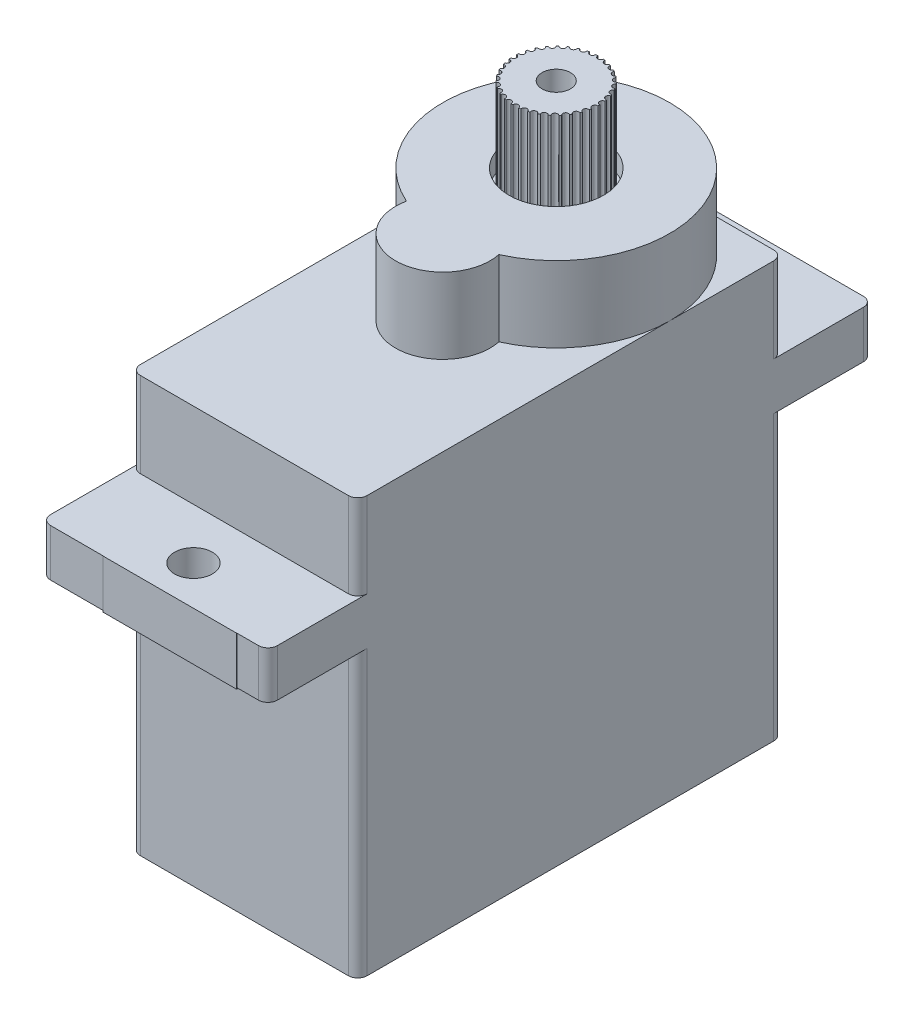
SolidWorks part; units mm, degrees
material "ABS PC"
ref_plane "Ön Düzlem" through (0, 0, 0) normal (0, 0, 1) x (1, 0, 0)
ref_plane "Üst Düzlem" through (0, 0, 0) normal (0, 1, 0) x (1, 0, 0)
ref_plane "Sağ Düzlem" through (0, 0, 0) normal (1, 0, 0) x (0, 0, -1)
sketch "Çizim1" plane through (0, 0, 0) normal (0, 1, 0) x (1, 0, 0)
  line L1 (-5.5, 11.25) -> (5.5, 11.25)
  line L2 (-6, 10.75) -> (-6, -10.75)
  line L3 (-5.5, -11.25) -> (5.5, -11.25)
  line L4 (6, 10.75) -> (6, -10.75)
  line L5 (-6, 11.25) -> (6, -11.25) construction
  line L6 (-6, -11.25) -> (6, 11.25) construction
  arc A0 (5.5, -11.25) -> (6, -10.75) centre (5.5, -10.75) ccw
  arc A1 (-6, -10.75) -> (-5.5, -11.25) centre (-5.5, -10.75) ccw
  arc A2 (5.5, 11.25) -> (6, 10.75) centre (5.5, 10.75) cw
  arc A3 (-5.5, 11.25) -> (-6, 10.75) centre (-5.5, 10.75) ccw
  point P0 (0, 0)
  dimension "D3" = 0.5
  dimension "D1" = 12
  dimension "D2" = 22.5
extrude "Yükseklik-Ekstrüzyon1" add sketch "Çizim1" along normal blind 1
sketch "Çizim2" plane through (0, 1, 0) normal (0, 1, 0) x (1, 0, 0)
  line L0 (-5, 9.25) -> (-5, -9.25)
  line L1 (-5.5, 11.25) -> (5.5, 11.25)
  line L2 (-6, 10.75) -> (-6, -10.75)
  line L3 (-5.5, -11.25) -> (5.5, -11.25)
  line L4 (6, 10.75) -> (6, -10.75)
  line L5 (-6, 11.25) -> (-5.8961, 11.0552) construction
  line L6 (-6, -11.25) -> (-5.8961, -11.0552) construction
  line L7 (-4, -10.25) -> (4, -10.25)
  line L8 (5, 9.25) -> (5, -9.25)
  line L9 (-4, 10.25) -> (4, 10.25)
  line L10 (-6, -11.25) -> (6, -11.25) construction
  line L11 (6, 11.25) -> (6, -11.25) construction
  line L12 (-6, 11.25) -> (-6, -11.25) construction
  line L13 (-6, 11.25) -> (6, 11.25) construction
  line L14 (-5, 10.25) -> (5, 10.25) construction
  line L15 (-5, 10.25) -> (-5, -10.25) construction
  line L16 (-4.9345, 9.2521) -> (4.9345, -9.2521) construction
  line L17 (5, 10.25) -> (5, -10.25) construction
  line L18 (5.8961, 11.0552) -> (6, 11.25) construction
  line L19 (-5, -10.25) -> (5, -10.25) construction
  line L20 (5.8961, -11.0552) -> (6, -11.25) construction
  line L21 (-4.9345, -9.2521) -> (4.9345, 9.2521) construction
  arc A0 (5.5, -11.25) -> (6, -10.75) centre (5.5, -10.75) ccw
  arc A1 (-6, -10.75) -> (-5.5, -11.25) centre (-5.5, -10.75) ccw
  arc A2 (5.5, 11.25) -> (6, 10.75) centre (5.5, 10.75) cw
  arc A3 (-5.5, 11.25) -> (-6, 10.75) centre (-5.5, 10.75) ccw
  arc A5 (4, 10.25) -> (5, 9.25) centre (5, 10.25) ccw
  arc A7 (-4, -10.25) -> (-5, -9.25) centre (-5, -10.25) ccw
  arc A8 (-5, 9.25) -> (-4, 10.25) centre (-5, 10.25) ccw
  arc A9 (5, -9.25) -> (4, -10.25) centre (5, -10.25) ccw
  point P0 (0, 0)
  dimension "D2" = 0.5
  dimension "D1" = 1
extrude "Yükseklik-Ekstrüzyon2" add sketch "Çizim2" along normal blind 5
sketch "Çizim3" plane through (0, 6, 0) normal (0, 1, 0) x (1, 0, 0)
  line L0 (0, -10.25) -> (0, -11.25) construction
  line L1 (-4, -10.25) -> (4, -10.25) construction
  line L2 (-5.5, -11.25) -> (5.5, -11.25) construction
  line L3 (0, -11.25) -> (0, -10.75) construction
  line L4 (0, -10.75) -> (2.4368, -10.75) construction
  line L6 (-2, -10.25) -> (2, -10.25)
  line L7 (-2, -10.25) -> (-2, -11.25)
  line L8 (-2, -11.25) -> (2, -11.25)
  line L9 (2, -10.25) -> (2, -11.25)
  line L10 (-2, -10.25) -> (2, -11.25) construction
  line L11 (-2, -11.25) -> (2, -10.25) construction
  dimension "D1" = 4
extrude "Kes-Ekstrüzyon1" cut sketch "Çizim3" against normal blind 1
fillet "Radyus1" radius 0.1 2 edges at (2, 5, 10.75) (-2, 5, 10.75)
sketch "Çizim4" plane through (0, 6, 0) normal (0, 1, 0) x (1, 0, 0)
  line L0 (-4, 10.25) -> (4, 10.25)
  line L1 (-5.5, 11.25) -> (5.5, 11.25)
  line L2 (-6, 10.75) -> (-6, -10.75)
  line L3 (-5.5, -11.25) -> (5.5, -11.25)
  line L4 (6, 10.75) -> (6, -10.75)
  line L5 (-6, 11.25) -> (-5.8961, 11.0552) construction
  line L6 (-6, -11.25) -> (-5.8961, -11.0552) construction
  line L7 (-4, 10.25) -> (4, 10.25)
  line L8 (5, 9.25) -> (5, -9.25)
  line L9 (5, -9.25) -> (5, 9.25)
  line L10 (-4, 10.25) -> (4, 10.25)
  line L11 (5, 9.25) -> (5, -9.25)
  line L12 (-4, -10.25) -> (4, -10.25)
  line L13 (-5, 9.25) -> (-5, -9.25)
  line L14 (-4.9345, 9.2521) -> (4.9345, -9.2521) construction
  line L15 (-5, 10.25) -> (-5, -10.25) construction
  line L16 (-5, 10.25) -> (5, 10.25) construction
  line L17 (5, 10.25) -> (5, -10.25) construction
  line L18 (5.8961, 11.0552) -> (6, 11.25) construction
  line L19 (5.8961, -11.0552) -> (6, -11.25) construction
  line L20 (-5, -10.25) -> (5, -10.25) construction
  line L21 (-4.9345, -9.2521) -> (4.9345, 9.2521) construction
  arc A0 (5.5, -11.25) -> (6, -10.75) centre (5.5, -10.75) ccw
  arc A1 (-6, -10.75) -> (-5.5, -11.25) centre (-5.5, -10.75) ccw
  arc A2 (5.5, 11.25) -> (6, 10.75) centre (5.5, 10.75) cw
  arc A3 (-5.5, 11.25) -> (-6, 10.75) centre (-5.5, 10.75) ccw
  arc A4 (-5, 9.25) -> (-4, 10.25) centre (-5, 10.25) ccw
  arc A5 (4, 10.25) -> (5, 9.25) centre (5, 10.25) ccw
  arc A6 (-4, -10.25) -> (-5, -9.25) centre (-5, -10.25) ccw
  arc A7 (5, -9.25) -> (4, -10.25) centre (5, -10.25) ccw
  arc A8 (5, 10.25) -> (5, 10.25) centre (5, 10.25) cw
  arc A9 (5, -10.25) -> (5, -10.25) centre (5, -10.25) ccw
  arc A10 (-5, -10.25) -> (-5, -10.25) centre (-5, -10.25) ccw
  arc A11 (-5, 10.25) -> (-5, 10.25) centre (-5, 10.25) ccw
  point P0 (0, 0)
  line M12 (4, -10.25) -> (2, -10.25)
  line M14 (2, -11.25) -> (5.5, -11.25)
  arc M15 (5.5, -11.25) -> (6, -10.75) centre (5.5, -10.75) ccw
  line M16 (6, -10.75) -> (6, 10.75)
  arc M17 (6, 10.75) -> (5.5, 11.25) centre (5.5, 10.75) ccw
  line M18 (5.5, 11.25) -> (-5.5, 11.25)
  arc M19 (-5.5, 11.25) -> (-6, 10.75) centre (-5.5, 10.75) ccw
  line M20 (-6, 10.75) -> (-6, -10.75)
  arc M21 (-6, -10.75) -> (-5.5, -11.25) centre (-5.5, -10.75) ccw
  line M22 (-5.5, -11.25) -> (-2, -11.25)
  line M24 (-2, -10.25) -> (-4, -10.25)
  arc M25 (-4, -10.25) -> (-5, -9.25) centre (-5, -10.25) ccw
  line M26 (-5, -9.25) -> (-5, 9.25)
  arc M27 (-5, 9.25) -> (-4, 10.25) centre (-5, 10.25) ccw
  line M28 (-4, 10.25) -> (4, 10.25)
  arc M29 (4, 10.25) -> (5, 9.25) centre (5, 10.25) ccw
  line M30 (5, 9.25) -> (5, -9.25)
  arc M31 (5, -9.25) -> (4, -10.25) centre (5, -10.25) ccw
  dimension "D1" = 0.5
  dimension "D2" = 1
extrude "Yükseklik-Ekstrüzyon4" add sketch "Çizim4" along normal blind 9 contours M31 M12 M14 M15 M16 M17 M18 M19 M20 M21 M22 M24 M25 M26 M27 M28 M29 M30 | L12 L3 region at (0, 6, -10.995)
sketch "Çizim6" plane through (0, 15, 0) normal (0, 1, 0) x (1, 0, 0)
  line L0 (0, -10.25) -> (0, -12.25) construction
  line L1 (-5.5, 16) -> (-0.7, 16)
  line L2 (-6, 15.5) -> (-6, -15.5)
  line L3 (-5.5, -16) -> (-0.7, -16)
  line L4 (6, 15.5) -> (6, -15.5)
  line L5 (-6, 16) -> (6, -16) construction
  line L6 (-3.8437, -10.25) -> (6, 16) construction
  line L7 (-4, 10.25) -> (4, 10.25)
  line L8 (-5, 9.25) -> (-5, -9.25)
  line L9 (-4, -10.25) -> (4, -10.25)
  line L10 (5, 9.25) -> (5, -9.25)
  line L11 (-4.5616, 9.3512) -> (4.5616, -9.3512) construction
  line L12 (-4.5616, -9.3512) -> (4.5616, 9.3512) construction
  line L13 (0, -12.25) -> (0, -11.25) construction
  line L14 (-5.5, -11.25) -> (5.5, -11.25) construction
  line L15 (0, -11.25) -> (8.7476, -11.25) construction
  line L16 (0, -12.25) -> (8.7476, -12.25) construction
  line L17 (0.7, -16) -> (5.5, -16)
  line L18 (-0.5, -14.2247) -> (-0.5, -15.8)
  line L19 (0.5, -14.2247) -> (0.5, -15.8)
  line L20 (0, 0) -> (5, 0) construction
  line L21 (0.5, 14.2247) -> (0.5, 15.8)
  line L22 (-0.5, 14.2247) -> (-0.5, 15.8)
  line L23 (0.7, 16) -> (5.5, 16)
  arc A0 (-5, 9.25) -> (-4, 10.25) centre (-5, 10.25) ccw
  arc A1 (4, 10.25) -> (5, 9.25) centre (5, 10.25) ccw
  arc A2 (5, -9.25) -> (4, -10.25) centre (5, -10.25) ccw
  arc A3 (-4, -10.25) -> (-5, -9.25) centre (-5, -10.25) ccw
  arc A4 (5.5, -16) -> (6, -15.5) centre (5.5, -15.5) ccw
  arc A5 (-6, -15.5) -> (-5.5, -16) centre (-5.5, -15.5) ccw
  arc A6 (5.5, 16) -> (6, 15.5) centre (5.5, 15.5) cw
  arc A7 (-5.5, 16) -> (-6, 15.5) centre (-5.5, 15.5) ccw
  arc A9 (0.5833, -14.0622) -> (-0.5833, -14.0622) centre (0, -13.25) ccw
  arc A10 (0.5, -14.2247) -> (0.5833, -14.0622) centre (0.7, -14.2247) cw
  arc A11 (-0.5, -14.2247) -> (-0.5833, -14.0622) centre (-0.7, -14.2247) ccw
  arc A12 (0.5, -15.8) -> (0.7, -16) centre (0.7, -15.8) ccw
  arc A13 (-0.5, -15.8) -> (-0.7, -16) centre (-0.7, -15.8) cw
  arc A14 (0.5, 15.8) -> (0.7, 16) centre (0.7, 15.8) cw
  arc A15 (-0.5, 15.8) -> (-0.7, 16) centre (-0.7, 15.8) ccw
  arc A16 (0.5, 14.2247) -> (0.5833, 14.0622) centre (0.7, 14.2247) ccw
  arc A17 (-0.5, 14.2247) -> (-0.5833, 14.0622) centre (-0.7, 14.2247) cw
  arc A18 (0.5833, 14.0622) -> (-0.5833, 14.0622) centre (0, 13.25) cw
  point P0 (0, 0)
  point P6 (0, 0)
  point P54 (0.5, -16)
  dimension "D2" = 0.5
  dimension "D4" = 2
  dimension "D5" = 0.2
  dimension "D1" = 32
  dimension "D3" = 1
extrude "Yükseklik-Ekstrüzyon5" add sketch "Çizim6" along normal blind 2.5
sketch "Çizim7" plane through (0, 17.5, 0) normal (0, 1, 0) x (1, 0, 0)
  line L0 (6, -15.5) -> (6, 15.5) construction
  line L1 (-5.5, 11.25) -> (5.5, 11.25)
  line L2 (-6, 10.75) -> (-6, -10.75)
  line L3 (-5.5, -11.25) -> (5.5, -11.25)
  line L4 (6, 10.75) -> (6, -10.75)
  line L5 (-6, 11.25) -> (-5.8961, 11.0552) construction
  line L6 (-6, -11.25) -> (-5.8961, -11.0552) construction
  line L7 (-5, 9.25) -> (-5, -9.25)
  line L8 (-4, 10.25) -> (4, 10.25)
  line L9 (5, 9.25) -> (5, -9.25)
  line L10 (4, -10.25) -> (-4, -10.25)
  line L12 (-4.9345, 9.2521) -> (4.9345, -9.2521) construction
  line L13 (5.8961, 11.0552) -> (6, 11.25) construction
  line L14 (5.8961, -11.0552) -> (6, -11.25) construction
  line L15 (-5, -9.25) -> (-5, 9.25)
  line L16 (-4.9345, -9.2521) -> (4.9345, 9.2521) construction
  line L17 (-5, 9.25) -> (-5, -9.25)
  arc A0 (-6, -10.75) -> (-5.5, -11.25) centre (-5.5, -10.75) ccw
  arc A1 (5.5, -11.25) -> (6, -10.75) centre (5.5, -10.75) ccw
  arc A2 (5.5, 11.25) -> (6, 10.75) centre (5.5, 10.75) cw
  arc A3 (-5.5, 11.25) -> (-6, 10.75) centre (-5.5, 10.75) ccw
  arc A4 (-5, 9.25) -> (-4, 10.25) centre (-5, 10.25) ccw
  arc A5 (4, 10.25) -> (5, 9.25) centre (5, 10.25) ccw
  arc A6 (5, -9.25) -> (4, -10.25) centre (5, -10.25) ccw
  arc A8 (-4, -10.25) -> (-5, -9.25) centre (-5, -10.25) ccw
  point P0 (0, 0)
  line M16 (6, -15.5) -> (6, 15.5)
  line M28 (-6, 15.5) -> (-6, -15.5)
  line M39 (-5, -9.25) -> (-5, 9.25)
  arc M40 (-5, 9.25) -> (-4, 10.25) centre (-5, 10.25) ccw
  line M41 (-4, 10.25) -> (4, 10.25)
  arc M42 (4, 10.25) -> (5, 9.25) centre (5, 10.25) ccw
  line M43 (5, 9.25) -> (5, -9.25)
  arc M44 (5, -9.25) -> (4, -10.25) centre (5, -10.25) ccw
  line M45 (4, -10.25) -> (-4, -10.25)
  arc M46 (-4, -10.25) -> (-5, -9.25) centre (-5, -10.25) ccw
  dimension "D2" = 0.5
  dimension "D1" = 22.5
extrude "Yükseklik-Ekstrüzyon6" add sketch "Çizim7" along normal blind 3.5 contours L1 A3 A0 L3 A1 A2 M28 M16 M46 M39 M40 M41 M42 M43 M44 M45 region at (0, 17.5, -10.995)
sketch "Çizim8" plane through (0, 21, 0) normal (0, 1, 0) x (1, 0, 0)
  line L0 (6, -15.5) -> (6, -10.75) construction
  line L1 (-5.5, 11.25) -> (5.5, 11.25)
  line L2 (-6, 10.75) -> (-6, -10.75)
  line L3 (-5.5, -11.25) -> (5.5, -11.25)
  line L4 (6, 10.75) -> (6, -10.75)
  line L5 (-6, 11.25) -> (6, -11.25) construction
  line L6 (-6, -11.25) -> (6, 11.25) construction
  arc A0 (-6, -10.75) -> (-5.5, -11.25) centre (-5.5, -10.75) ccw
  arc A1 (5.5, -11.25) -> (6, -10.75) centre (5.5, -10.75) ccw
  arc A2 (5.5, 11.25) -> (6, 10.75) centre (5.5, 10.75) cw
  arc A3 (-5.5, 11.25) -> (-6, 10.75) centre (-5.5, 10.75) ccw
  point P0 (0, 0)
  dimension "D1" = 0.5
extrude "Yükseklik-Ekstrüzyon7" add sketch "Çizim8" along normal blind 1
sketch "Çizim9" plane through (0, 22, 0) normal (0, 1, 0) x (1, 0, 0)
  line L0 (-6, 5.25) -> (6, 5.25) construction
  line L1 (-6, 10.75) -> (-6, -10.75) construction
  line L2 (6, -10.75) -> (6, 10.75) construction
  line L3 (5.5, 11.25) -> (-5.5, 11.25) construction
  line L4 (0, 5.25) -> (0, -0.75) construction
  arc A0 (2.4451, -0.2292) -> (-2.4451, -0.2292) centre (0, 5.25) ccw
  arc A1 (-2.4451, -0.2292) -> (2.4451, -0.2292) centre (0, -0.75) ccw
  arc A2 (1.0153, 0.3542) -> (-1.0153, 0.3542) centre (0, 5.25) ccw
  arc A3 (-1.0153, 0.3542) -> (1.0153, 0.3542) centre (0, -0.75) ccw
  dimension "D2" = 5
  dimension "D1" = 6
  dimension "D3" = 1
extrude "Kes-Ekstrüzyon2" cut sketch "Çizim9" against normal blind 1 contours A2 A3
extrude "Yükseklik-Ekstrüzyon8" add sketch "Çizim9<3>" along normal blind 3
sketch "Çizim9<3>" plane through (0, 22, 0) normal (0, 1, 0) x (1, 0, 0) same geometry as "Çizim9"
fillet "Radyus2" radius 0.5 2 edges at (1.0153, 23, -0.3542) (-1.0153, 23, -0.3542)
sketch "Çizim10" plane through (0, 25, 0) normal (0, 1, 0) x (1, 0, 0)
  arc A0 (2.4451, -0.2292) -> (-2.4451, -0.2292) centre (0, 5.25) ccw
  arc A1 (-2.4451, -0.2292) -> (2.4451, -0.2292) centre (0, -0.75) ccw
extrude "Yükseklik-Ekstrüzyon9" add sketch "Çizim10" along normal blind 1
sketch "Çizim11" plane through (0, 26, 0) normal (0, 1, 0) x (1, 0, 0)
  circle A0 centre (0, 5.25) radius 2.5
  dimension "D1" = 5
extrude "Kes-Ekstrüzyon3" cut sketch "Çizim11" against normal blind 10
sketch "Çizim15" plane through (0, 26, 0) normal (0, 1, 0) x (1, 0, 0)
  circle A0 centre (0, -0.75) radius 0.25
  dimension "D1" = 0.5
extrude "Yükseklik-Ekstrüzyon12" add sketch "Çizim15" against normal blind 11
ref_plane "Düzlem3" through (0, 30, 0) normal (0, 1, 0) x (1, 0, 0)
sketch "Çizim19" plane through (0, 30, 0) normal (0, 1, 0) x (1, 0, 0)
  circle A0 centre (0, 5.25) radius 2.25
  dimension "D1" = 4.5
extrude "Yükseklik-Ekstrüzyon17" add sketch "Çizim19" against normal blind 5 separate body
sketch "Çizim20" plane through (0, 25, 0) normal (0, -1, 0) x (1, 0, 0)
  circle A0 centre (0, -5.25) radius 4.75
  dimension "D1" = 9.5
extrude "Yükseklik-Ekstrüzyon18" add sketch "Çizim20" along normal blind 3
sketch "Çizim21" plane through (0, 30, 0) normal (0, 1, 0) x (1, 0, 0)
  circle A0 centre (0, 5.25) radius 0.75
  dimension "D1" = 1.5
extrude "Kes-Ekstrüzyon5" cut sketch "Çizim21" against normal blind 10
ref_plane "Düzlem4" through (0, 25.5, 0) normal (0, 1, 0) x (1, 0, 0)
sketch "Çizim22" plane through (0, 25.5, 0) normal (0, 1, 0) x (1, 0, 0)
  line L0 (0, 11.25) -> (0, -3.25) construction
  arc A0 (2.4451, -0.2292) -> (-2.4451, -0.2292) centre (0, 5.25) ccw construction
  arc A1 (-2.4451, -0.2292) -> (2.4451, -0.2292) centre (0, -0.75) ccw construction
  circle A2 centre (0, -0.75) radius 0.5
  dimension "D1" = 1
extrude "Yükseklik-Ekstrüzyon19" add sketch "Çizim22" against normal blind 5
sketch "Çizim23" plane through (0, 20.5, 0) normal (0, -1, 0) x (1, 0, 0)
  circle A0 centre (0, 0.75) radius 4
  dimension "D1" = 8
extrude "Yükseklik-Ekstrüzyon20" add sketch "Çizim23" along normal blind 2
sketch "Çizim24" plane through (0, 22, 0) normal (0, -1, 0) x (1, 0, 0)
  circle A0 centre (0, -5.25) radius 0.75
extrude "Yükseklik-Ekstrüzyon21" add sketch "Çizim24" along normal blind 7 separate body
ref_plane "Düzlem5" through (0, 19, 0) normal (0, -1, 0) x (-1, 0, 0)
sketch "Çizim25" plane through (0, 19, 0) normal (0, -1, 0) x (-1, 0, 0)
  circle A0 centre (0, 5.25) radius 3.5
  dimension "D1" = 7
extrude "Yükseklik-Ekstrüzyon22" add sketch "Çizim25" along normal blind 1
ref_plane "Düzlem6" through (0, 17.5, 0) normal (0, -1, 0) x (-1, 0, 0)
sketch "Çizim26" plane through (0, 17.5, 0) normal (0, -1, 0) x (-1, 0, 0)
  circle A0 centre (0, -0.75) radius 4.5
  dimension "D1" = 9
extrude "Yükseklik-Ekstrüzyon23" add sketch "Çizim26" along normal blind 1
sketch "Çizim32" plane through (0, 0, 10.25) normal (0, 0, -1) x (-1, 0, 0)
  line L1 (2, 6) -> (-2, 6)
  line L2 (2, 6) -> (2, 5.1)
  line L3 (1.9, 5) -> (-1.9, 5)
  line L4 (-2, 6) -> (-2, 5.1)
  arc A0 (-1.9, 5) -> (-2, 5.1) centre (-1.9, 5.1) cw
  arc A1 (2, 5.1) -> (1.9, 5) centre (1.9, 5.1) cw
  point P7 (-2, 5)
  dimension "D3" = 0.1
  dimension "D1" = 1
  dimension "D2" = 4
extrude "Kes-Ekstrüzyon7" cut sketch "Çizim32" along normal blind 30
sketch "Çizim33" plane through (0, 0, 11.25) normal (0, 0, 1) x (1, 0, 0)
  line L1 (-2, 6) -> (2, 6)
  line L2 (-2, 6) -> (-2, 5.1)
  line L3 (-1.9, 5) -> (1.9, 5)
  line L4 (2, 6) -> (2, 5.1)
  arc A0 (1.9, 5) -> (2, 5.1) centre (1.9, 5.1) ccw
  arc A1 (-2, 5.1) -> (-1.9, 5) centre (-1.9, 5.1) ccw
  point P7 (2, 5)
  point P10 (-2, 5)
  dimension "D3" = 0.1
  dimension "D1" = 1
  dimension "D2" = 4
extrude "Yükseklik-Ekstrüzyon33" add sketch "Çizim33" against normal blind 1
sketch "Çizim34" plane through (0, 1, 0) normal (0, 1, 0) x (1, 0, 0)
  line L0 (-5, -6.25) -> (5, -6.25) construction
  line L1 (-5, 9.25) -> (-5, -9.25) construction
  line L2 (5, -9.25) -> (5, 9.25) construction
  line L3 (-4, -10.25) -> (4, -10.25) construction
  line L5 (-3, -3.25) -> (3, -3.25)
  line L6 (-4, -4.25) -> (-4, -8.25)
  line L7 (-3, -9.25) -> (3, -9.25)
  line L8 (4, -4.25) -> (4, -8.25)
  line L9 (-4, -3.25) -> (4, -9.25) construction
  line L10 (-4, -9.25) -> (4, -3.25) construction
  arc A0 (3, -9.25) -> (4, -8.25) centre (3, -8.25) ccw
  arc A1 (-4, -8.25) -> (-3, -9.25) centre (-3, -8.25) ccw
  arc A2 (3, -3.25) -> (4, -4.25) centre (3, -4.25) cw
  arc A3 (-3, -3.25) -> (-4, -4.25) centre (-3, -4.25) ccw
  point P8 (0, -6.25)
  dimension "D4" = 1
  dimension "D1" = 4
  dimension "D2" = 6
  dimension "D3" = 8
extrude "Yükseklik-Ekstrüzyon34" add sketch "Çizim34" along normal blind 14
ref_plane "Düzlem8" through (0, 1, 0) normal (0, -1, 0) x (-1, 0, 0)
sketch "Çizim37" plane through (0, 1, 0) normal (0, -1, 0) x (-1, 0, 0)
  line L0 (4, -6.25) -> (-4, -6.25) construction
  line L1 (4, -4.25) -> (4, -8.25) construction
  line L2 (-4, -8.25) -> (-4, -4.25) construction
  line L4 (4, -9.25) -> (-4, -9.25)
  line L5 (4, -9.25) -> (4, -3.25)
  line L6 (4, -3.25) -> (-4, -3.25)
  line L7 (-4, -9.25) -> (-4, -3.25)
  line L8 (4, -9.25) -> (-4, -3.25) construction
  line L9 (4, -3.25) -> (-4, -9.25) construction
  point P6 (0, -6.25)
  dimension "D1" = 6
  dimension "D2" = 8
extrude "Yükseklik-Ekstrüzyon36" add sketch "Çizim37" against normal blind 1
ref_plane "Düzlem9" through (0, 0, -10.75) normal (0, 0, -1) x (-1, 0, 0)
sketch "Çizim39" plane through (0, 0, -10.75) normal (0, 0, -1) x (-1, 0, 0)
  line L0 (0, 0) -> (0, 6.0146) construction
  line L1 (-5.5, 0) -> (5.5, 0) construction
  line L2 (-2, 6.0146) -> (2, 6.0146)
  line L4 (-2, 6.0146) -> (-2, 5.0146)
  line L5 (-2, 5.0146) -> (2, 5.0146)
  line L6 (2, 6.0146) -> (2, 5.0146)
  line L7 (0, 6.0146) -> (2, 5.0146) construction
  line L8 (-2, 5.0146) -> (0, 6.0146) construction
extrude "Yükseklik-Ekstrüzyon37" add sketch "Çizim39" along normal blind 0.1
sketch "Çizim40" plane through (0, 0, -10.85) normal (0, 0, -1) x (-1, 0, 0)
  line L0 (-2, 5.55) -> (2, 5.55) construction
  line L1 (-2, 6) -> (-2, 5.1) construction
  line L2 (2, 5.1) -> (2, 6) construction
  circle A0 centre (0, 5.55) radius 0.4
  circle A1 centre (1, 5.55) radius 0.4
  circle A2 centre (-1, 5.55) radius 0.4
  dimension "D1" = 0.8
  dimension "D2" = 1
  dimension "D3" = 1
extrude "Yükseklik-Ekstrüzyon38" add sketch "Çizim40" along normal blind 2
sketch "Çizim41" plane through (0, 30, 0) normal (0, 1, 0) x (1, 0, 0)
  line L0 (0, 5.25) -> (-2.25, 5.25) construction
  circle A0 centre (0, 5.25) radius 2.25
  circle A1 centre (-2.25, 5.25) radius 0.15
  circle A2 centre (-2.2138, 5.6518) radius 0.15
  circle A3 centre (-2.1065, 6.0406) radius 0.15
  circle A4 centre (-1.9315, 6.404) radius 0.15
  circle A5 centre (-1.6944, 6.7304) radius 0.15
  circle A6 centre (-1.4029, 7.0091) radius 0.15
  circle A7 centre (-1.0662, 7.2313) radius 0.15
  circle A8 centre (-0.6953, 7.3899) radius 0.15
  circle A9 centre (-0.302, 7.4796) radius 0.15
  circle A10 centre (0.1009, 7.4977) radius 0.15
  circle A11 centre (0.5007, 7.4436) radius 0.15
  circle A12 centre (0.8843, 7.3189) radius 0.15
  circle A13 centre (1.2395, 7.1278) radius 0.15
  circle A14 centre (1.5549, 6.8763) radius 0.15
  circle A15 centre (1.8203, 6.5725) radius 0.15
  circle A16 centre (2.0272, 6.2262) radius 0.15
  circle A17 centre (2.1689, 5.8486) radius 0.15
  circle A18 centre (2.2409, 5.4517) radius 0.15
  circle A19 centre (2.2409, 5.0483) radius 0.15
  circle A20 centre (2.1689, 4.6514) radius 0.15
  circle A21 centre (2.0272, 4.2738) radius 0.15
  circle A22 centre (1.8203, 3.9275) radius 0.15
  circle A23 centre (1.5549, 3.6237) radius 0.15
  circle A24 centre (1.2395, 3.3722) radius 0.15
  circle A25 centre (0.8843, 3.1811) radius 0.15
  circle A26 centre (0.5007, 3.0564) radius 0.15
  circle A27 centre (0.1009, 3.0023) radius 0.15
  circle A28 centre (-0.302, 3.0204) radius 0.15
  circle A29 centre (-0.6953, 3.1101) radius 0.15
  circle A30 centre (-1.0662, 3.2687) radius 0.15
  circle A31 centre (-1.4029, 3.4909) radius 0.15
  circle A32 centre (-1.6944, 3.7696) radius 0.15
  circle A33 centre (-1.9315, 4.096) radius 0.15
  circle A34 centre (-2.1065, 4.4594) radius 0.15
  circle A35 centre (-2.2138, 4.8482) radius 0.15
  point P75 (0, 5.25)
  circle M3 centre (0, 5.25) radius 2.25
  dimension "D1" = 0.3
  dimension "D2" = 35
extrude "Kes-Ekstrüzyon8" cut sketch "Çizim41" against normal blind 5 contours A1 A0 M3 | A1 L0 A0 | L0 A1 M3 | A3 | A2 | A35 | A34 | A33 | A32 | A31 | A30 | A29 | A28 | A27 | A26 | A25 | A24 | A23 | A22 | A21 | A20 | A19 | A18 | A17 | A16 | A15 | A14 | A13 | A12 | A11 | A10 | A9 | A8 | A7 | A6 | A5 | A4 region at (-2.1854, 30, -5.187) region at (-2.1854, 30, -5.313) region at (-2.3128, 30, -5.25)
sketch "Sketch1" plane through (6, 0, 0) normal (1, 0, 0) x (0, 0, -1)
  line L0 (-11.25, 15) -> (-11.25, 17.5)
  line L1 (-11.25, 17.5) -> (-15.392, 18.5248)
  line L2 (-15.392, 18.5248) -> (-18.0744, 15.6606)
  line L3 (-18.0744, 15.6606) -> (-16.9833, 13.1147)
  line L4 (-16.9833, 13.1147) -> (-11.25, 15)
  line L5 (11.25, 17.5) -> (15.2512, 19.7037)
  line L6 (15.2512, 19.7037) -> (17.7477, 16.5229)
  line L7 (17.7477, 16.5229) -> (17.3909, 13.5625)
  line L8 (17.3909, 13.5625) -> (13.5869, 13.2571)
  line L9 (13.5869, 13.2571) -> (11.25, 15)
  line L10 (11.25, 15) -> (11.25, 17.5)
sketch "Sketch2" plane through (0, 30, 0) normal (0, 1, 0) x (1, 0, 0)
  line L0 (0.75, 5.25) -> (-0.75, 5.25)
  line L1 (0, 4.5) -> (0, 6)
  circle A0 centre (0, 5.25) radius 0.75 construction
sketch "Sketch3" plane through (0, 17.5, 0) normal (0, 1, 0) x (1, 0, 0)
  line L1 (5.5, 16) -> (-5.5, 16)
  line L2 (5.5, 16) -> (5.5, -16)
  line L3 (5.5, -16) -> (-5.5, -16)
  line L4 (-5.5, 16) -> (-5.5, -16)
  line L5 (5.5, 16) -> (-5.5, -16) construction
  line L6 (5.5, -16) -> (-5.5, 16) construction
  point P0 (0, 0)
sketch "Sketch4" plane through (0, 17.5, 0) normal (0, 1, 0) x (1, 0, 0)
  line L1 (-2.7094, -11.6117) -> (4.3529, -11.6117)
  line L2 (-2.7094, -11.6117) -> (-2.7094, -16.0101)
  line L3 (-2.7094, -16.0101) -> (4.3529, -16.0101)
  line L4 (4.3529, -11.6117) -> (4.3529, -16.0101)
extrude "Boss-Extrude6" add sketch "Sketch4" against normal blind 2.57
sketch "Sketch5" plane through (0, 17.5, 0) normal (0, 1, 0) x (1, 0, 0)
  line L0 (5.5, 16) -> (-5.5, 16) construction
  line L1 (-2.5368, 11.7643) -> (3.8827, 11.7643)
  line L2 (-2.5368, 11.7643) -> (-2.5368, 16)
  line L3 (-2.5368, 16) -> (3.8827, 16)
  line L4 (3.8827, 11.7643) -> (3.8827, 16)
extrude "Boss-Extrude7" add sketch "Sketch5" against normal blind 2.57
sketch "Sketch6" plane through (0, 17.5, 0) normal (0, 1, 0) x (1, 0, 0)
  line L0 (0, 13.94) -> (0, -13.94) construction
  circle A0 centre (0, -13.94) radius 1
  circle A1 centre (0, 13.94) radius 1
  point P4 (0, 0)
  dimension "D2" = 2
  dimension "D3" = 2
  dimension "D1" = 27.88
extrude "Cut-Extrude1" cut sketch "Sketch6" against normal blind 12.57
